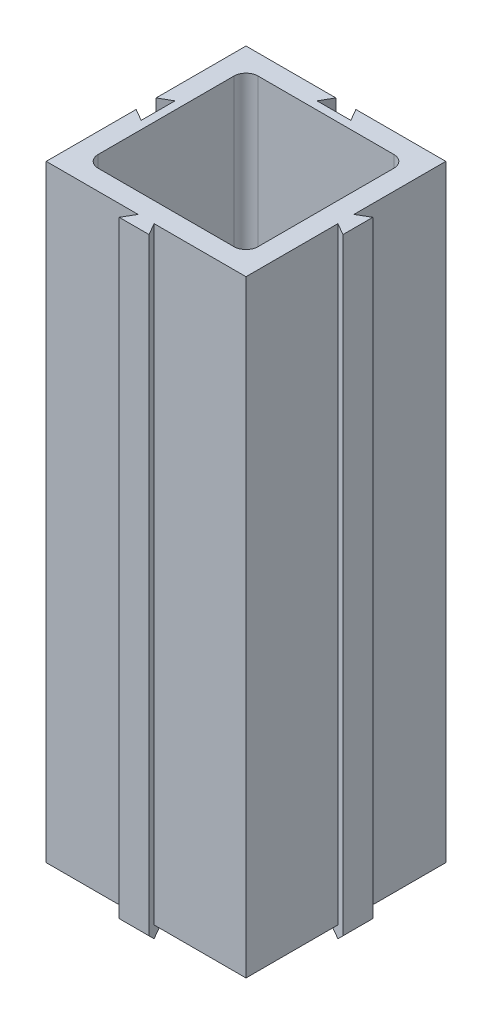
SolidWorks part; units mm, degrees
ref_plane "Front Plane" through (0, 0, 0) normal (0, 0, 1) x (1, 0, 0)
ref_plane "Top Plane" through (0, 0, 0) normal (0, 1, 0) x (1, 0, 0)
ref_plane "Right Plane" through (0, 0, 0) normal (1, 0, 0) x (0, 0, -1)
sketch "Sketch1" plane through (0, 0, 0) normal (0, 1, 0) x (1, 0, 0)
  line L0 (-11, 2.116) -> (-11, -2.116)
  line L3 (0, 16.0204) -> (0, -19.6084) construction
  line L5 (18.0663, 0) -> (-17.4129, 0) construction
  line L6 (-11, -2.116) -> (-12.5, -1.25)
  line L7 (-12.5, -1.25) -> (-12.5, -12.5)
  line L8 (-12.5, 1.25) -> (-12.5, 12.5)
  line L9 (-11, 2.116) -> (-12.5, 1.25)
  line L10 (0, 0) -> (-12.5, 12.5) construction
  line L11 (-2.116, 11) -> (-1.25, 12.5)
  line L12 (-1.25, 12.5) -> (-12.5, 12.5)
  line L13 (1.25, 12.5) -> (12.5, 12.5)
  line L14 (2.116, 11) -> (1.25, 12.5)
  line L15 (-2.116, 11) -> (2.116, 11)
  line L16 (-12.5, -12.5) -> (-1, -12.5)
  line L17 (-1, -12.5) -> (-1.866, -14)
  line L18 (-1.866, -14) -> (1.866, -14)
  line L19 (1, -12.5) -> (1.866, -14)
  line L20 (12.5, -12.5) -> (1, -12.5)
  line L21 (-16.0204, 0) -> (19.6084, 0) construction
  line L22 (12.5, -12.5) -> (12.5, -1)
  line L23 (12.5, -1) -> (14, -1.866)
  line L24 (14, 1.866) -> (14, -1.866)
  line L25 (12.5, 1) -> (14, 1.866)
  line L26 (12.5, 12.5) -> (12.5, 1)
  line L27 (-2.116, 21.0883) -> (-2.116, -12.7995) construction
  line L28 (1.25, 18.3402) -> (1.25, -13.7995) construction
  line L29 (-10, 10) -> (-10, -10)
  line L30 (-10, 10) -> (10, 10)
  line L31 (-10, -10) -> (10, -10)
  line L32 (10, 10) -> (10, -10)
  point P12 (-11, 0)
  point P13 (0, 11)
  point P23 (0, -14)
  point P31 (14, 0)
  point P40 (-10, 0)
  point P42 (0, -10)
  point P43 (0, 10)
  dimension "D1" = 60
  dimension "D2" = 2.5
  dimension "D3" = 25
  dimension "D4" = 1.5
  dimension "D5" = 45
  dimension "D6" = 0.5
  dimension "D7" = 60
  dimension "D8" = 0.5
  dimension "D9" = 20
extrude "Boss-Extrude1" add sketch "Sketch1" along normal blind 77.5
sketch "Sketch2" plane through (0, 0, 0) normal (0, 1, 0) x (1, 0, 0)
  line L0 (10, 10) -> (10, -10)
  line L1 (10, -10) -> (-10, -10)
  line L2 (-10, -10) -> (-10, 10)
  line L3 (-10, 10) -> (10, 10)
extrude "Boss-Extrude2" add sketch "Sketch2" along normal blind 2.5
sketch "Sketch3" plane through (0, 2.5, 0) normal (0, 1, 0) x (1, 0, 0)
  line L0 (0, 14.7677) -> (0, 0) construction
  line L1 (0, 0) -> (-17.9797, 0) construction
  line L2 (0, 0) -> (-14.7542, 14.7542) construction
  circle A0 centre (-6, 6) radius 1.5
  circle A1 centre (6, 6) radius 1.5
  circle A2 centre (6, -6) radius 1.5
  circle A3 centre (-6, -6) radius 1.5
  point P6 (0, 0)
  dimension "D3" = 3
  dimension "D1" = 45
  dimension "D2" = 6
extrude "Cut-Extrude1" cut sketch "Sketch3" against normal through all both and the other way through all
chamfer "Chamfer1" distance 1.5 angle 45 12 edges at (14, 0, 0) (12.5, 0, -6.75) (6.875, 0, -12.5) (0, 0, -11) (0, 0, 14) (12.5, 0, 6.75) (6.75, 0, 12.5) (-11, 0, 0) (-6.75, 0, 12.5) (-12.5, 0, 6.875) (-6.875, 0, -12.5) (-12.5, 0, -6.875)
chamfer "Chamfer2" distance 1 angle 45 8 edges at (10, 2.5, 0) (0, 2.5, 10) (-10, 2.5, 0) (0, 2.5, -10) (-6, 2.5, -7.5) (6, 2.5, -7.5) (6, 2.5, 4.5) (-6, 2.5, 4.5)
fillet "Fillet1" radius 1.5 4 edges at (10, 40.5, -10) (10, 40.5, 10) (-10, 40.5, -10) (-10, 40.5, 10)
